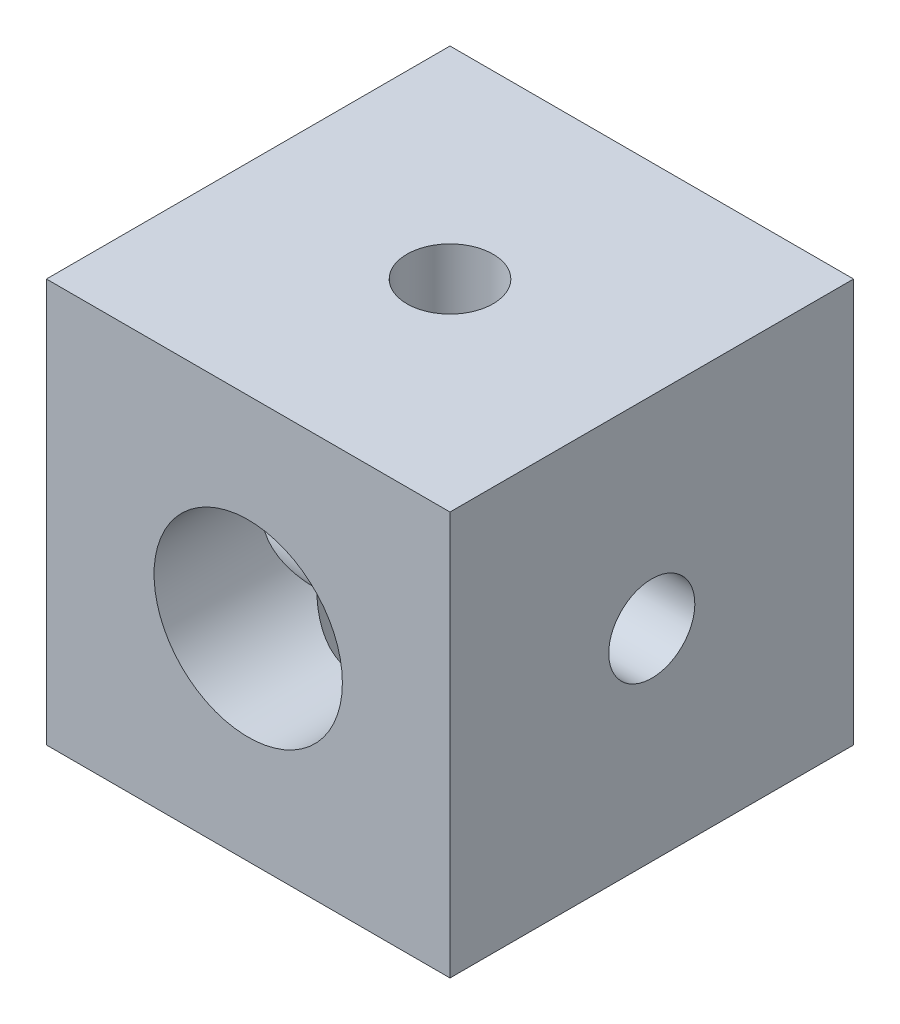
SolidWorks part; units mm, degrees
ref_plane "Plano frontal" through (0, 0, 0) normal (0, 0, 1) x (1, 0, 0)
ref_plane "Plano superior" through (0, 0, 0) normal (0, 1, 0) x (1, 0, 0)
ref_plane "Plano direito" through (0, 0, 0) normal (1, 0, 0) x (0, 0, -1)
sketch "Esboço1" plane through (0, 0, 0) normal (0, 0, 1) x (1, 0, 0)
  line L1 (-7.5, 7.5) -> (7.5, 7.5)
  line L2 (-7.5, 7.5) -> (-7.5, -7.5)
  line L3 (-7.5, -7.5) -> (7.5, -7.5)
  line L4 (7.5, 7.5) -> (7.5, -7.5)
  line L5 (-7.5, 7.5) -> (7.5, -7.5) construction
  line L6 (-7.5, -7.5) -> (7.5, 7.5) construction
  circle A0 centre (0, 0) radius 1.6
  circle A1 centre (0, 0) radius 3.5
  point P0 (0, 0)
  dimension "D1" = 3.2
  dimension "D3" = 7
  dimension "D2" = 15
extrude "Ressalto-extrusão1" add sketch "Esboço1" along normal mid plane 15 contours L4 L1 L2 L3 A1 region at (0, 7.2879, 0)
sketch "Esboço2" plane through (7.5, 0, 0) normal (1, 0, 0) x (0, 0, -1)
  line L0 (-7.5, 7.5) -> (7.5, -7.5) construction
  circle A0 centre (0, 0) radius 3.5
  circle A1 centre (0, 0) radius 1.6
  dimension "D1" = 3.2
  dimension "D2" = 7
extrude "Corte-extrusão1" cut sketch "Esboço2" against normal through all contours A0
sketch "Esboço4" plane through (0, 7.5, 0) normal (0, 1, 0) x (1, 0, 0)
  circle A0 centre (0, 0) radius 3.5
  circle A1 centre (0, 0) radius 1.6
  dimension "D1" = 7
  dimension "D2" = 3.2
extrude "Corte-extrusão2" cut sketch "Esboço4" against normal through all both and the other way through all contours A0
extrude "Ressalto-extrusão2" add sketch "Esboço1<3>" along normal blind 3 from surface contours A1 A0 region at (-3.401, 0, 0) starting at face at (3.5, 0, -7.5)
sketch "Esboço1<3>" plane through (0, 0, 0) normal (0, 0, 1) x (1, 0, 0) same geometry as "Esboço1"
extrude "Ressalto-extrusão3" add sketch "Esboço2<3>" against normal blind 3
sketch "Esboço2<3>" plane through (7.5, 0, 0) normal (1, 0, 0) x (0, 0, -1) same geometry as "Esboço2"
extrude "Ressalto-extrusão4" add sketch "Esboço4<3>" against normal blind 3
sketch "Esboço4<3>" plane through (0, 7.5, 0) normal (0, 1, 0) x (1, 0, 0) same geometry as "Esboço4"
